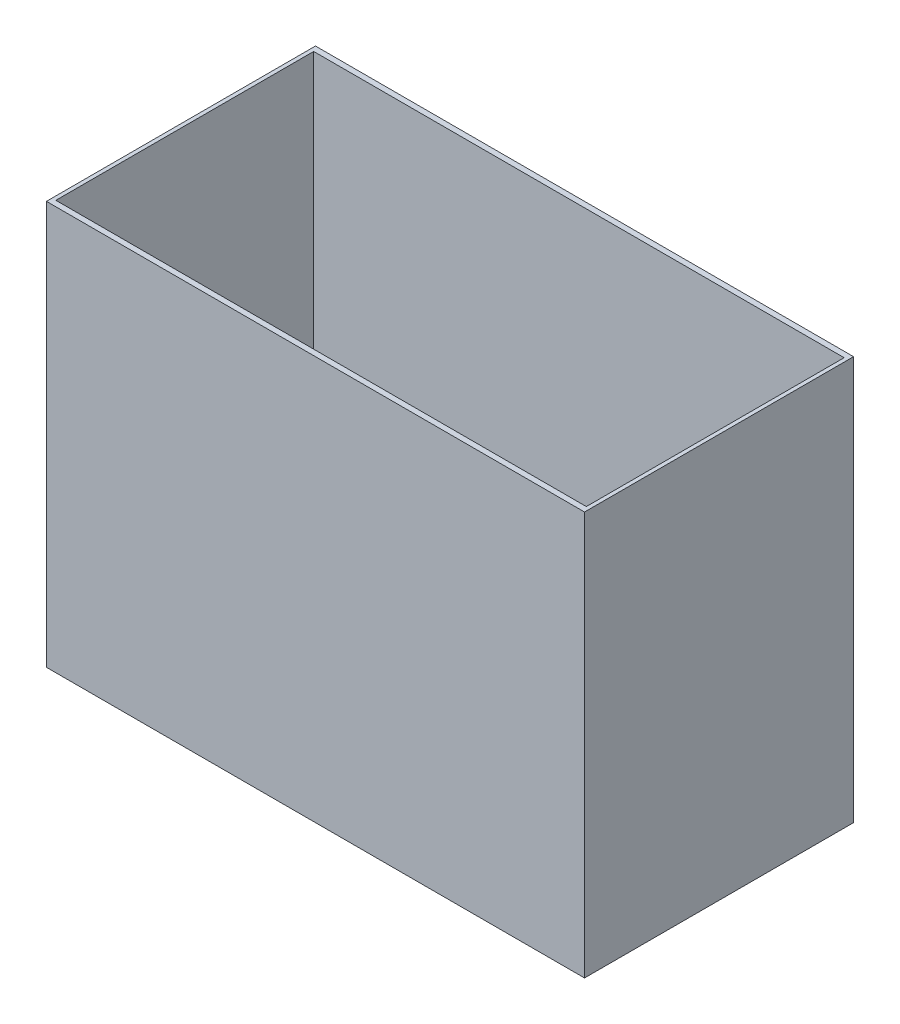
SolidWorks part; units mm, degrees
ref_plane "Front Plane" through (0, 0, 0) normal (0, 0, 1) x (1, 0, 0)
ref_plane "Top Plane" through (0, 0, 0) normal (0, 1, 0) x (1, 0, 0)
ref_plane "Right Plane" through (0, 0, 0) normal (1, 0, 0) x (0, 0, -1)
other "Bounding Box"
ref_plane "Default Plane" through (-292.1, 0, -139.7) normal (0, 1, 0) x (1, 0, 0)
sketch "Sketch1" plane through (0, 0, 0) normal (0, 1, 0) x (1, 0, 0)
  line L0 (-292.1, 0) -> (292.1, 0) construction
  line L1 (-292.1, 139.7) -> (292.1, 139.7)
  line L2 (-292.1, 139.7) -> (-292.1, -139.7)
  line L3 (-292.1, -139.7) -> (292.1, -139.7)
  line L4 (292.1, 139.7) -> (292.1, -139.7)
  line L5 (0, 139.7) -> (0, -139.7) construction
  point P8 (0, 0)
  dimension "D1" = 584.2
  dimension "D2" = 279.4
extrude "Boss-Extrude1" add sketch "Sketch1" along normal blind 12.7
sketch "Sketch2" plane through (0, 12.7, 0) normal (0, 1, 0) x (1, 0, 0)
  line L0 (-245.9259, -63.5) -> (-55.3589, -63.5) construction
  line L1 (-241.3, -120.6497) -> (-152.4, -120.6497)
  line L2 (-241.3, -120.6497) -> (-241.3, -101.5997)
  line L3 (-241.3, -101.5997) -> (-152.4, -101.5997)
  line L4 (-152.4, -120.6497) -> (-152.4, -101.5997)
  line L5 (-241.3, -120.6497) -> (-152.4, -101.5997) construction
  line L6 (-241.3, -101.5997) -> (-152.4, -120.6497) construction
  line L7 (-292.1, 139.7) -> (-292.1, -139.7) construction
  line L8 (-292.1, 0) -> (292.1, 0) construction
  line L9 (292.1, -139.7) -> (292.1, 139.7) construction
  line L10 (0, 0) -> (0, 121.6784) construction
  line L11 (241.3, -101.5997) -> (152.4, -120.6497) construction
  line L12 (241.3, -120.6497) -> (152.4, -101.5997) construction
  line L13 (152.4, -120.6497) -> (152.4, -101.5997)
  line L14 (241.3, -101.5997) -> (152.4, -101.5997)
  line L15 (241.3, -120.6497) -> (241.3, -101.5997)
  line L16 (241.3, -120.6497) -> (152.4, -120.6497)
  point P0 (-196.85, -111.1247)
  point P17 (196.85, -111.1247)
  dimension "D1" = 19.05
  dimension "D2" = 88.9
  dimension "D3" = 38.0997
  dimension "D4" = 50.8
  dimension "D5" = 63.5
extrude "Boss-Extrude2" [suppressed] add sketch "Sketch2" along normal blind 304.8 separate body contours L2 L1 L4 L3
pattern_linear "LPattern1" [suppressed] count 2 spacing 304.8 of bodies 101
pattern_linear "LPattern2" [suppressed] count 2 spacing 215.9 of bodies 101
sketch "Sketch3" plane through (0, 0, 0) normal (0, 1, 0) x (1, 0, 0)
  line L1 (-304.8, -152.4) -> (304.8, -152.4)
  line L2 (-304.8, -152.4) -> (-304.8, 152.4)
  line L3 (-304.8, 152.4) -> (304.8, 152.4)
  line L4 (304.8, -152.4) -> (304.8, 152.4)
  line L5 (-304.8, -152.4) -> (304.8, 152.4) construction
  line L6 (-304.8, 152.4) -> (304.8, -152.4) construction
  line L7 (-300.482, -146.05) -> (300.482, -146.05)
  line L8 (-300.482, -146.05) -> (-300.482, 146.05)
  line L9 (-300.482, 146.05) -> (300.482, 146.05)
  line L10 (300.482, -146.05) -> (300.482, 146.05)
  line L11 (-300.482, -146.05) -> (300.482, 146.05) construction
  line L12 (-300.482, 146.05) -> (300.482, -146.05) construction
  point P0 (0, 0)
  point P6 (0, 0)
  dimension "D1" = 609.6
  dimension "D2" = 304.8
  dimension "D3" = 292.1
  dimension "D4" = 600.964
extrude "Boss-Extrude3" add sketch "Sketch3" along normal blind 457.2 separate body
sketch "Sketch4" plane through (0, 12.7, 0) normal (0, 1, 0) x (1, 0, 0)
  circle A0 centre (273.05, 120.65) radius 2.7781
  circle A1 centre (273.05, 120.65) radius 4 construction
  circle A2 centre (273.05, 120.65) radius 4 construction
  dimension "D1" = 5.5562
extrude "Cut-Extrude1" cut sketch "Sketch4" against normal through all
sketch "Sketch6" plane through (0, 0, 0) normal (0, -1, 0) x (1, 0, 0)
  circle A0 centre (273.05, -120.65) radius 6.35
  circle A1 centre (273.05, -120.65) radius 2.7781 construction
  dimension "D1" = 12.7
extrude "Cut-Extrude2" cut sketch "Sketch6" against normal blind 2.54
mirror "Mirror1" about plane through (0, 0, 0) normal (0, 0, 1) of "Cut-Extrude2", "Cut-Extrude1"
sketch "Sketch7" plane through (0, 12.7, 0) normal (0, 1, 0) x (1, 0, 0)
  line L0 (292.1, 0) -> (49.4912, 0) construction
  line L1 (292.1, -139.7) -> (292.1, 139.7) construction
  circle A0 centre (190.5, 0) radius 4 construction
  circle A1 centre (190.5, 0) radius 2.7781
  dimension "D1" = 8
  dimension "D2" = 5.5562
  dimension "D3" = 101.6
extrude "Cut-Extrude3" cut sketch "Sketch7" against normal through all
sketch "Sketch8" plane through (0, 12.7, 0) normal (0, 1, 0) x (1, 0, 0)
  circle A0 centre (94.9, -12.8415) radius 1.9844 construction
  circle A1 centre (146.1, -12.8415) radius 1.9844 construction
  circle A2 centre (146.1, 12.8415) radius 1.9844 construction
  circle A3 centre (94.9, 12.8415) radius 1.9844 construction
  circle A4 centre (94.9, -12.8415) radius 1.9844
  circle A5 centre (146.1, -12.8415) radius 1.9844
  circle A6 centre (146.1, 12.8415) radius 1.9844
  circle A7 centre (94.9, 12.8415) radius 1.9844
extrude "Cut-Extrude4" cut sketch "Sketch8" against normal through all
sketch "Sketch9" plane through (0, 0, 0) normal (0, -1, 0) x (1, 0, 0)
  circle A1 centre (190.5, 0) radius 6.35
  circle A2 centre (146.1, 12.8415) radius 6.35
  circle A3 centre (94.9, 12.8415) radius 6.35
  circle A4 centre (94.9, -12.8415) radius 6.35
  circle A5 centre (146.1, -12.8415) radius 6.35
  circle A6 centre (273.05, 120.65) radius 6.35 construction
extrude "Cut-Extrude5" cut sketch "Sketch9" against normal blind 3.175
